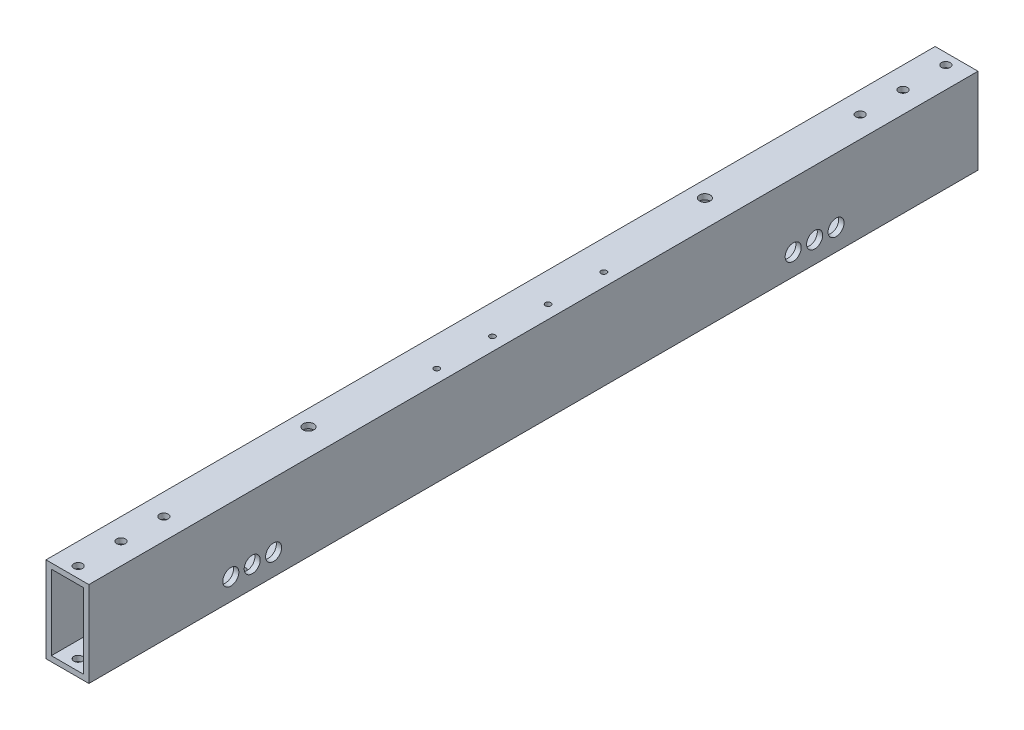
SolidWorks part; units mm, degrees
material "6061-T6 (SS)"
ref_plane "Front" through (0, 0, 0) normal (0, 0, 1) x (1, 0, 0)
ref_plane "Top" through (0, 0, 0) normal (0, 1, 0) x (1, 0, 0)
ref_plane "Right" through (0, 0, 0) normal (1, 0, 0) x (0, 0, -1)
sketch "Sketch1" plane through (0, 0, 0) normal (0, 0, 1) x (1, 0, 0)
  line L1 (-12.7, -25.4) -> (12.7, -25.4)
  line L2 (-12.7, -25.4) -> (-12.7, 25.4)
  line L3 (-12.7, 25.4) -> (12.7, 25.4)
  line L4 (12.7, -25.4) -> (12.7, 25.4)
  line L5 (-12.7, -25.4) -> (12.7, 25.4) construction
  line L6 (-12.7, 25.4) -> (12.7, -25.4) construction
  point P0 (0, 0)
  dimension "D1" = 25.4
  dimension "D2" = 50.8
extrude "Extrude-Thin1" add sketch "Sketch1" along normal blind 527.05 thin thin type one direction reverse wall 3.175
hole_wizard "#10 Clearance Hole1" positions "Sketch2" profile "Sketch3" hole size "#10" standard "ANSI Inch" end condition through all
sketch "Sketch2" plane through (0, 25.4, 0) normal (0, 1, 0) x (1, 0, 0)
  line L0 (12.7, -527.05) -> (-12.7, -527.05) construction
  line L1 (-12.7, -527.05) -> (-12.7, 0) construction
  point P0 (0, -520.7)
  point P2 (0, -495.3)
  point P4 (0, -469.9)
  point P13 (0, -6.35)
  point P15 (0, -31.75)
  point P17 (0, -57.15)
  dimension "D1" = 6.35
  dimension "D2" = 25.4
  dimension "D3" = 25.4
  dimension "D4" = 12.7
  dimension "D5" = 6.35
  dimension "D6" = 25.4
  dimension "D7" = 25.4
sketch "Sketch3" plane through (0, 25.4, 520.7) normal (1, 0, 0) x (0, 0, 1)
  line L0 (0, 0) -> (0, 50.8)
  line L1 (0, 50.8) -> (2.5527, 50.8)
  line L2 (2.5527, 50.8) -> (2.5527, 0)
  line L5 (2.5527, 0) -> (0, 0)
  line L11 (0, -6.35) -> (0, 107.95) construction
  dimension "Thru Hole Dia." = 5.1054
  dimension "Thru Hole Depth" = 50.8
sketch "Sketch8" plane through (0, -25.4, 0) normal (0, -1, 0) x (-1, 0, 0)
  point P0 (3.175, -451.358)
  point P3 (-3.175, -425.958)
  point P6 (3.175, -400.558)
  point P9 (-3.175, -375.158)
  point P12 (3.175, -349.758)
  point P19 (3.175, -298.958)
  point P26 (3.175, -248.158)
  point P29 (-3.175, -222.758)
  point P32 (3.175, -197.358)
  point P35 (-3.175, -171.958)
  point P38 (3.175, -146.558)
  point P41 (-3.175, -121.158)
  point P48 (-3.175, -70.358)
  point P55 (-3.175, -324.358)
  point P58 (-3.175, -273.558)
  point P61 (3.175, -95.758)
hole_wizard "1/8 (0.13) Diameter Hole1" positions "Sketch8" profile "Sketch7" hole size "1/8" standard "ANSI Inch" end condition up to next
sketch "Sketch7" plane through (-3.175, -25.4, 451.358) normal (1, 0, 0) x (0, 0, -1)
  line L0 (0, 0) -> (0, 3.175)
  line L1 (0, 3.175) -> (1.651, 3.175)
  line L2 (1.651, 3.175) -> (1.651, 0)
  line L5 (1.651, 0) -> (0, 0)
  line L11 (0, -6.35) -> (0, 107.95) construction
  dimension "Thru Hole Dia." = 3.302
  dimension "Thru Hole Depth" = 3.175
sketch "Sketch11" plane through (0, 25.4, 0) normal (0, 1, 0) x (1, 0, 0)
  point P0 (4.9212, -313.055)
  point P3 (4.9212, -280.035)
  point P6 (4.9212, -247.015)
  point P9 (4.9212, -213.995)
hole_wizard "1/8 (0.13) Diameter Hole2" positions "Sketch11" profile "Sketch10" hole size "1/8" standard "ANSI Inch" end condition up to next
sketch "Sketch10" plane through (4.9212, 25.4, 313.055) normal (1, 0, 0) x (0, 0, 1)
  line L0 (0, 0) -> (0, 3.175)
  line L1 (0, 3.175) -> (1.651, 3.175)
  line L2 (1.651, 3.175) -> (1.651, 0)
  line L5 (1.651, 0) -> (0, 0)
  line L11 (0, -6.35) -> (0, 107.95) construction
  dimension "Thru Hole Dia." = 3.302
  dimension "Thru Hole Depth" = 3.175
sketch "Sketch14" plane through (0, 25.4, 0) normal (0, 1, 0) x (1, 0, 0)
  line L0 (12.7, 0) -> (-12.7, 0) construction
  line L1 (12.7, -527.05) -> (-12.7, -527.05) construction
  line L2 (-12.7, -527.05) -> (-12.7, 0) construction
  point P0 (-3.175, -146.05)
  point P2 (-3.175, -381)
  dimension "D1" = 146.05
  dimension "D2" = 146.05
  dimension "D3" = 9.525
hole_wizard "1/4 (0.25) Diameter Hole1" positions "Sketch14" profile "Sketch13" hole size "1/4" standard "ANSI Inch"
sketch "Sketch13" plane through (-3.175, 25.4, 146.05) normal (1, 0, 0) x (0, 0, 1)
  line L0 (0, 0) -> (0, 12.6265)
  line L1 (0, 12.6265) -> (3.175, 10.7188)
  line L2 (3.175, 10.7188) -> (3.175, 0)
  line L5 (3.175, 0) -> (0, 0)
  line L10 (0, 12.6265) -> (-3.175, 10.7188) construction
  line L11 (0, -6.35) -> (0, 107.95) construction
  dimension "Hole Dia." = 6.35
  dimension "Hole Depth" = 10.7188
  dimension "Drill Angle" = 118
sketch "Sketch17" plane through (12.7, 0, 0) normal (1, 0, 0) x (0, 0, -1)
  point P38 (-84.1375, -12.7)
  point P41 (-96.8375, -12.7)
  point P44 (-109.5375, -12.7)
  point P48 (-417.5125, -12.7)
  point P51 (-442.9125, -12.7)
  point P54 (-430.2125, -12.7)
hole_wizard "CBORE for #10 Socket Head Cap Screw1" positions "Sketch17" profile "Sketch16" counterbore size "#10" standard "ANSI Inch" end condition through all
sketch "Sketch16" plane through (12.7, -12.7, 84.1375) normal (0, 1, 0) x (0, 0, -1)
  line L0 (0, 0) -> (0, 25.4)
  line L1 (0, 25.4) -> (2.5527, 25.4)
  line L3 (2.5527, 25.4) -> (2.5527, 8.001)
  line L4 (2.5527, 8.001) -> (4.7625, 8.001)
  line L5 (4.7625, 8.001) -> (4.7625, 0)
  line L7 (4.7625, 0) -> (0, 0)
  line L11 (0, -6.35) -> (0, 107.95) construction
  dimension "Thru Hole Dia." = 5.1054
  dimension "Thru Hole Depth" = 25.4
  dimension "C'Bore Dia." = 9.525
  dimension "C'Bore Depth" = 8.001
